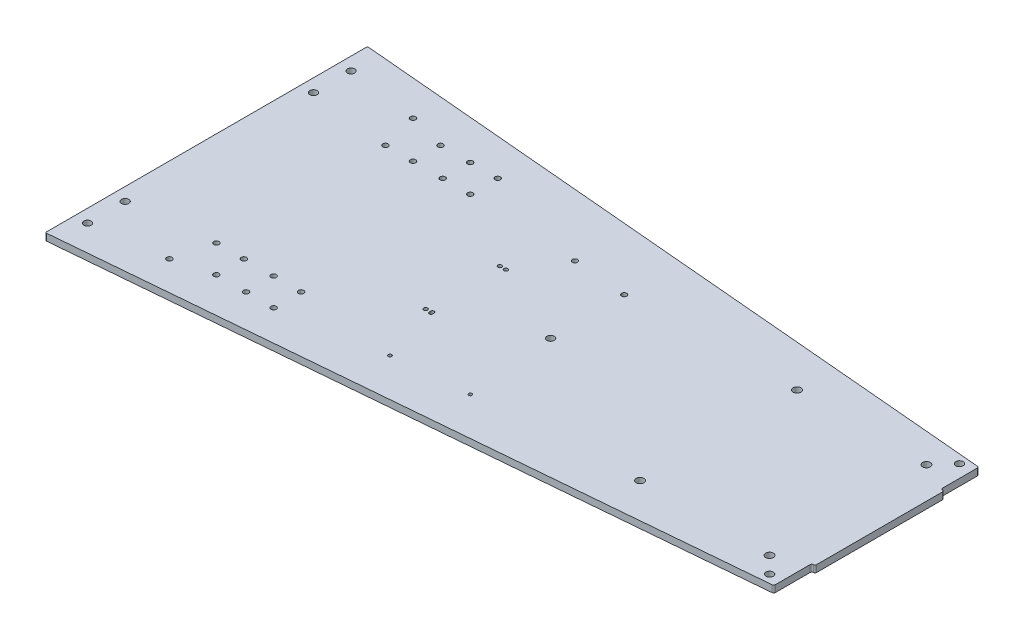
SolidWorks part; units mm, degrees
ref_plane "Front Plane" through (0, 0, 0) normal (0, 0, 1) x (1, 0, 0)
ref_plane "Top Plane" through (0, 0, 0) normal (0, 1, 0) x (1, 0, 0)
ref_plane "Right Plane" through (0, 0, 0) normal (1, 0, 0) x (0, 0, -1)
sketch "Sketch1" plane through (0, 0, 0) normal (0, 1, 0) x (1, 0, 0)
  line L0 (0, -94.3735) -> (0, 94.3735)
  line L1 (0, 94.3735) -> (-621.5262, 148.75)
  line L2 (-621.5262, 148.75) -> (-621.5262, -148.75)
  line L3 (-621.5262, -148.75) -> (0, -94.3735)
  point P7 (0, 0)
  dimension "D1" = 188.747
  dimension "D2" = 297.5
  dimension "D3" = 95
  dimension "D4" = 95
extrude "Boss-Extrude1" add sketch "Sketch1" along normal mid plane 6.35
hole_wizard "M3 Clearance Hole1" positions "Sketch8" profile "Sketch9" hole size "M3" standard "ANSI Metric" end condition through all
sketch "Sketch8" plane through (0, 3.175, 0) normal (0, 1, 0) x (1, 0, 0)
  point P0 (-379.222, 34.29)
  point P3 (-384.81, 34.29)
  point P6 (-384.81, -34.29)
sketch "Sketch9" plane through (-379.222, 3.175, -34.29) normal (1, 0, 0) x (0, 0, 1)
  line L0 (0, 0) -> (0, 6.35)
  line L1 (0, 6.35) -> (1.8, 6.35)
  line L2 (1.8, 6.35) -> (1.8, 0)
  line L5 (1.8, 0) -> (0, 0)
  line L11 (0, -6.35) -> (0, 107.95) construction
  dimension "Thru Hole Dia." = 3.6
  dimension "Thru Hole Depth" = 6.35
hole_wizard "1/4 Clearance Hole1" positions "Sketch10" profile "Sketch11" hole size "1/4" standard "ANSI Inch" end condition through all
sketch "Sketch10" plane through (0, 3.175, 0) normal (0, 1, 0) x (1, 0, 0)
  point P0 (-29.1473, 72.4527)
  point P3 (-29.1473, -72.4527)
  point P6 (-148.6527, -72.4527)
  point P9 (-148.6527, 72.4527)
sketch "Sketch11" plane through (-29.1473, 3.175, -72.4527) normal (1, 0, 0) x (0, 0, 1)
  line L0 (0, 0) -> (0, 6.35)
  line L1 (0, 6.35) -> (3.5712, 6.35)
  line L2 (3.5712, 6.35) -> (3.5712, 0)
  line L5 (3.5712, 0) -> (0, 0)
  line L11 (0, -6.35) -> (0, 107.95) construction
  dimension "Thru Hole Dia." = 7.1425
  dimension "Thru Hole Depth" = 6.35
sketch "Sketch12" plane through (0, 3.175, 0) normal (0, 1, 0) x (1, 0, 0)
  line L0 (-380.8412, -33.6169) -> (-380.8412, -34.0868) construction
  line L1 (-380.8412, -34.4932) -> (-380.8412, -34.9631) construction
  line L2 (-377.6027, -34.9631) -> (-377.6027, -34.4932) construction
  line L3 (-377.6027, -34.0868) -> (-377.6027, -33.6169) construction
  line L4 (-380.8412, -33.6169) -> (-380.8412, -34.0868)
  line L5 (-380.8412, -34.4932) -> (-380.8412, -34.9631)
  line L6 (-377.6027, -34.9631) -> (-377.6027, -34.4932)
  line L7 (-377.6027, -34.0868) -> (-377.6027, -33.6169)
  arc A0 (-380.8412, -34.0868) -> (-380.8412, -34.4932) centre (-379.222, -34.29) ccw construction
  arc A1 (-380.8412, -34.9631) -> (-377.6027, -34.9631) centre (-379.222, -34.9631) ccw construction
  arc A2 (-377.6027, -34.4932) -> (-377.6027, -34.0868) centre (-379.222, -34.29) ccw construction
  arc A3 (-377.6027, -33.6169) -> (-380.8412, -33.6169) centre (-379.222, -33.6169) ccw construction
  arc A4 (-380.8412, -34.0868) -> (-380.8412, -34.4932) centre (-379.222, -34.29) ccw
  arc A5 (-380.8412, -34.9631) -> (-377.6027, -34.9631) centre (-379.222, -34.9631) ccw
  arc A6 (-377.6027, -34.4932) -> (-377.6027, -34.0868) centre (-379.222, -34.29) ccw
  arc A7 (-377.6027, -33.6169) -> (-380.8412, -33.6169) centre (-379.222, -33.6169) ccw
extrude "Cut-Extrude1" cut sketch "Sketch12" against normal through all
hole_wizard "#8 Clearance Hole1" positions "Sketch13" profile "Sketch14" hole size "#8" standard "ANSI Inch" end condition through all
sketch "Sketch13" plane through (0, 3.175, 0) normal (0, 1, 0) x (1, 0, 0)
  point P0 (-508.8331, -78.0643)
  point P3 (-508.8331, -103.4643)
  point P6 (-543.2134, -112.4445)
  point P9 (-534.2331, -78.0643)
  point P12 (-481.4079, -78.0643)
  point P15 (-481.4079, -103.4643)
  point P18 (-456.0079, -78.0643)
  point P21 (-456.0079, -103.4643)
  point P24 (-456.0079, 78.0643)
  point P27 (-456.0079, 103.4643)
  point P30 (-481.4079, 78.0643)
  point P33 (-481.4079, 103.4643)
  point P36 (-543.2134, 112.4445)
  point P39 (-534.2331, 78.0643)
  point P42 (-508.8331, 103.4643)
  point P45 (-508.8331, 78.0643)
sketch "Sketch14" plane through (-508.8331, 3.175, 78.0643) normal (1, 0, 0) x (0, 0, 1)
  line L0 (0, 0) -> (0, 6.35)
  line L1 (0, 6.35) -> (2.4574, 6.35)
  line L2 (2.4574, 6.35) -> (2.4574, 0)
  line L5 (2.4574, 0) -> (0, 0)
  line L11 (0, -6.35) -> (0, 107.95) construction
  dimension "Thru Hole Dia." = 4.9149
  dimension "Thru Hole Depth" = 6.35
sketch "Sketch15" plane through (0, 3.175, 0) normal (0, 1, 0) x (1, 0, 0)
  circle A0 centre (-295.9182, -81.917) radius 1.55 construction
  circle A1 centre (-364.1575, -87.8871) radius 1.55 construction
  circle A6 centre (-295.9182, -81.917) radius 1.55
  circle A7 centre (-364.1575, -87.8871) radius 1.55
extrude "Cut-Extrude2" cut sketch "Sketch15" against normal through all
sketch "Sketch16" plane through (0, 3.175, 0) normal (0, 1, 0) x (1, 0, 0)
  circle A0 centre (-609.6, -121.6503) radius 3.3782 construction
  circle A1 centre (-609.6, -86.9431) radius 3.3782 construction
  circle A2 centre (-609.6, 86.9431) radius 3.3782 construction
  circle A3 centre (-609.6, 121.6503) radius 3.3782 construction
  circle A4 centre (-609.6, -121.6503) radius 3.3782
  circle A5 centre (-609.6, -86.9431) radius 3.3782
  circle A6 centre (-609.6, 86.9431) radius 3.3782
  circle A7 centre (-609.6, 121.6503) radius 3.3782
extrude "Cut-Extrude3" cut sketch "Sketch16" against normal through all
fillet "Fillet1" radius 1 2 edges at (-621.5262, 0, 148.75) (-621.5262, 0, -148.75)
sketch "Sketch17" plane through (0, 3.175, 0) normal (0, 1, 0) x (1, 0, 0)
  line L0 (-3, 94.636) -> (-3, 59.636)
  line L1 (0, 94.3735) -> (-620.4391, 148.6549) construction
  line L2 (-3, 59.636) -> (0, 59.636)
  line L3 (0, -94.3735) -> (0, 94.3735) construction
  line L4 (0, 59.636) -> (0, 94.3735)
  line L5 (0, 94.3735) -> (-3, 94.636)
  dimension "D1" = 3
  dimension "D2" = 35
extrude "Cut-Extrude4" cut sketch "Sketch17" against normal through all
mirror "Mirror1" about plane through (0, 0, 0) normal (0, 0, 1) of "Cut-Extrude4"
fillet "Fillet2" radius 1.5 6 edges at (0, 0, -59.636) (-3, 0, -59.636) (-3, 0, -94.636) (0, 0, 59.636) (-3, 0, 59.636) (-3, 0, 94.636)
hole_wizard "#13 (0.185) Diameter Hole1" positions "Sketch18" profile "Sketch20" hole size "#13" standard "ANSI Inch" end condition through all
sketch "Sketch18" plane through (0, 3.175, 0) normal (0, 1, 0) x (1, 0, 0)
  point P0 (-354.4456, 73.1877)
  point P3 (-304.6358, 68.83)
sketch "Sketch20" plane through (-354.4456, 3.175, -73.1877) normal (1, 0, 0) x (0, 0, 1)
  line L0 (0, 0) -> (0, 6.35)
  line L1 (0, 6.35) -> (2.3495, 6.35)
  line L2 (2.3495, 6.35) -> (2.3495, 0)
  line L5 (2.3495, 0) -> (0, 0)
  line L11 (0, -6.35) -> (0, 107.95) construction
  dimension "Thru Hole Dia." = 4.699
  dimension "Thru Hole Depth" = 6.35
hole_wizard "1/4 Clearance Hole2" positions "Sketch21" profile "Sketch22" hole size "1/4" standard "ANSI Inch" end condition through all
sketch "Sketch21" plane through (0, 3.175, 0) normal (0, 1, 0) x (1, 0, 0)
  point P0 (-14.732, 88.4699)
  point P3 (-14.0462, -87.4539)
  point P6 (-303.7332, 0)
sketch "Sketch22" plane through (-14.732, 3.175, -88.4699) normal (1, 0, 0) x (0, 0, 1)
  line L0 (0, 0) -> (0, 6.35)
  line L1 (0, 6.35) -> (3.3782, 6.35)
  line L2 (3.3782, 6.35) -> (3.3782, 0)
  line L5 (3.3782, 0) -> (0, 0)
  line L11 (0, -6.35) -> (0, 107.95) construction
  dimension "Thru Hole Dia." = 6.7564
  dimension "Thru Hole Depth" = 6.35
